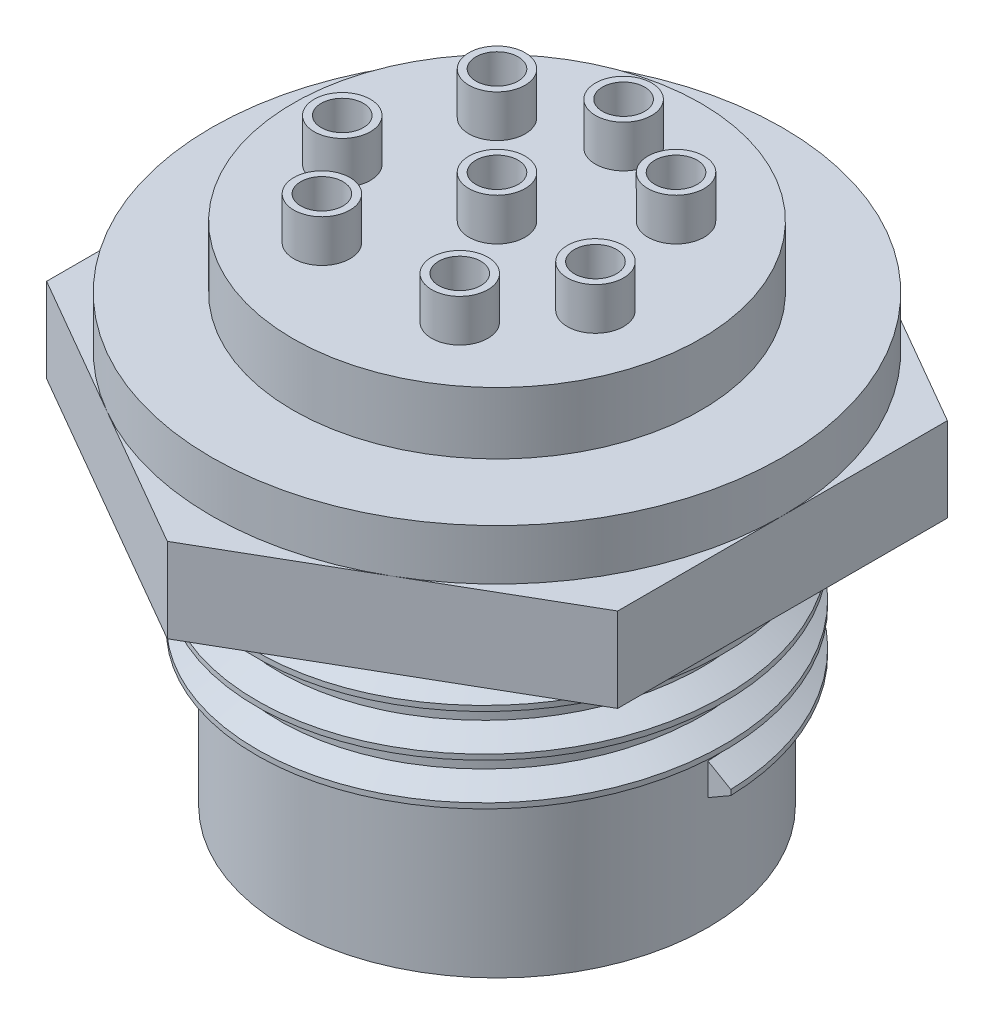
SolidWorks part; units mm, degrees
ref_plane "Front Plane" through (0, 0, 0) normal (0, 0, 1) x (1, 0, 0)
ref_plane "Top Plane" through (0, 0, 0) normal (0, 1, 0) x (1, 0, 0)
ref_plane "Right Plane" through (0, 0, 0) normal (1, 0, 0) x (0, 0, -1)
sketch "Sketch1" plane through (0, 0, 0) normal (0, 1, 0) x (1, 0, 0)
  circle A0 centre (0, 0) radius 7.25
  dimension "D1" = 14.5
extrude "Boss-Extrude1" add sketch "Sketch1" against normal blind 2.2
sketch "Sketch2" plane through (0, -2.2, 0) normal (0, -1, 0) x (1, 0, 0)
  circle A0 centre (0, 0) radius 10.15
  dimension "D1" = 20.3
extrude "Boss-Extrude2" add sketch "Sketch2" along normal blind 1.8
sketch "Sketch3" plane through (0, -4, 0) normal (0, -1, 0) x (1, 0, 0)
  line L1 (0, 11.7202) -> (-10.15, 5.8601)
  line L2 (-10.15, 5.8601) -> (-10.15, -5.8601)
  line L3 (-10.15, -5.8601) -> (0, -11.7202)
  line L4 (0, -11.7202) -> (10.15, -5.8601)
  line L5 (10.15, -5.8601) -> (10.15, 5.8601)
  line L6 (10.15, 5.8601) -> (0, 11.7202)
  circle A0 centre (0, 0) radius 10.15 construction
  dimension "D1" = 20.3
  dimension "D2" = 5.8601
extrude "Boss-Extrude3" add sketch "Sketch3" along normal blind 3
sketch "Sketch4" plane through (0, -7, 0) normal (0, -1, 0) x (1, 0, 0)
  circle A0 centre (0, 0) radius 7.5
  dimension "D1" = 15
extrude "Boss-Extrude4" add sketch "Sketch4" along normal blind 6
thread "Thread1" pitch 1.5 method extrude profile "Thread Profile1" start angle 0, offset 1, length 6, pitch 1.5, diameter 15
ref_plane "Plane1" through (7.5, -14, 0) normal (0, 0, 1) x (1, 0, 0)
sketch "Thread Profile1" plane through (7.5, -14, 0) normal (0, 0, 1) x (1, 0, 0)
  line L0 (0, 0) -> (0, 1.5) construction
  line L1 (0, 0) -> (0.8119, 0.4687)
  line L2 (0.8119, 0.4687) -> (0.8119, 0.6562)
  line L3 (0.8119, 0.6562) -> (0, 1.125)
  line L4 (0.8119, 0.5625) -> (0, 0.5625) construction
  line L11 (0, 0) -> (0, 1.125)
  point P2 (0, 0)
  dimension "Pitch" = 1.5
  dimension "Profile_Angle" = 60
  dimension "Profile_Land" = 0.1875
  dimension "Profile_Height" = 0.8119
sketch "Sketch13" plane through (0, -13, 0) normal (0, -1, 0) x (-1, 0, 0)
  circle A0 centre (0, 0) radius 7.5
  circle A1 centre (0, 0) radius 6.5
  dimension "D1" = 13
extrude "Boss-Extrude5" add sketch "Sketch13" along normal blind 5
sketch "Sketch15" plane through (0, -13, 0) normal (0, -1, 0) x (1, 0, 0)
  line L0 (0, 0) -> (0, -6.5) construction
  line L1 (0, 0) -> (-4.5962, -4.5962) construction
  line L2 (-6.5, 0) -> (6.5, 0) construction
  line L3 (0, 0) -> (-3.5402, 5.4514) construction
  circle A0 centre (0, 0) radius 1
  circle A1 centre (0, 0) radius 6.5 construction
  circle A2 centre (0, -4.5) radius 1
  circle A3 centre (0, 0) radius 6.5 construction
  circle A4 centre (-3.182, -3.182) radius 1
  circle A5 centre (3.182, -3.182) radius 1
  circle A6 centre (-4.5, 1) radius 1
  circle A8 centre (-2.4509, 3.774) radius 1
  circle A9 centre (4.5, 1) radius 1
  circle A10 centre (2.4509, 3.774) radius 1
  dimension "D1" = 2
  dimension "D2" = 2
  dimension "D3" = 2
  dimension "D5" = 2
  dimension "D6" = 2
  dimension "D7" = 2
  dimension "D8" = 1
  dimension "D9" = 2
  dimension "D10" = 2
  dimension "D11" = 2
  dimension "D4" = 45
  dimension "D13" = 57
extrude "Boss-Extrude6" add sketch "Sketch15" along normal blind 4 and the other way blind 14.5 separate body
sketch "Sketch16" plane through (0, 1.5, 0) normal (0, 1, 0) x (1, 0, 0)
  circle A0 centre (0, 0) radius 0.75
  circle A1 centre (-4.5, -1) radius 0.75
  circle A2 centre (-3.182, 3.182) radius 0.75
  circle A3 centre (0, 4.5) radius 0.75
  circle A4 centre (3.182, 3.182) radius 0.75
  circle A5 centre (4.5, -1) radius 0.75
  circle A6 centre (2.4509, -3.774) radius 0.75
  circle A7 centre (-2.4509, -3.774) radius 0.75
  dimension "D1" = 1.5
  dimension "D2" = 1.5
  dimension "D3" = 1.5
  dimension "D4" = 1.5
  dimension "D5" = 1.5
  dimension "D6" = 1.5
  dimension "D7" = 1.5
  dimension "D8" = 1.5
extrude "Cut-Extrude1" cut sketch "Sketch16" against normal blind 1.4
fillet "Fillet1" radius 0.5 1 edges at (-2.4509, -17, 2.774)
fillet "Fillet2" radius 0.5 1 edges at (-4.5, -17, 0)
fillet "Fillet3" radius 0.5 1 edges at (0, -17, -1)
fillet "Fillet4" radius 0.5 1 edges at (2.4509, -17, 4.774)
fillet "Fillet5" radius 0.5 1 edges at (4.5, -17, 2)
fillet "Fillet6" radius 0.5 1 edges at (-3.182, -17, -4.182)
fillet "Fillet7" radius 0.5 1 edges at (0, -17, -5.5)
fillet "Fillet8" radius 0.5 1 edges at (3.182, -17, -2.182)
